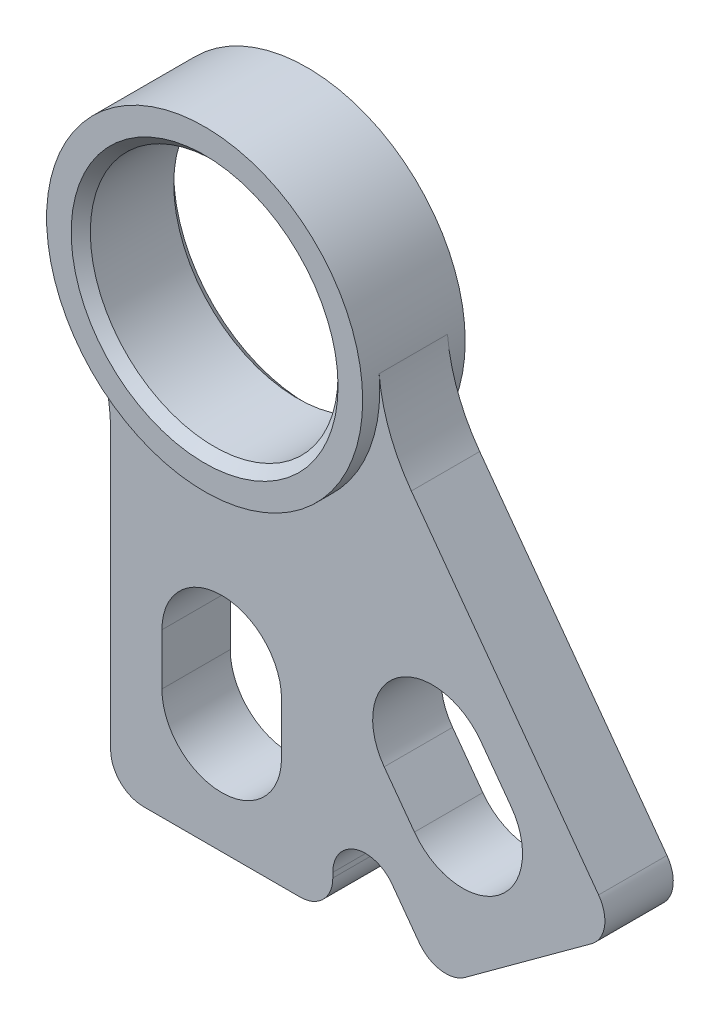
SolidWorks part; units mm, degrees
material "AISI 4130 Steel, annealed at 865C"
ref_plane "X-Y Datum" through (0, 0, 0) normal (0, 0, 1) x (1, 0, 0)
ref_plane "X-Z Datum" through (0, 0, 0) normal (0, 1, 0) x (1, 0, 0)
ref_plane "Y-Z Datum" through (0, 0, 0) normal (1, 0, 0) x (0, 0, -1)
sketch "Sketch1" plane through (0, 0, 0) normal (0, 0, 1) x (1, 0, 0)
  line L0 (0, -34.1313) -> (0, -29.3687) construction
  line L1 (-5.5562, -34.1313) -> (-5.5562, -29.3687)
  line L2 (5.5562, -34.1313) -> (5.5562, -29.3687)
  line L3 (22.3879, -30.632) -> (19.5777, -26.787) construction
  line L4 (17.902, -33.9106) -> (15.0918, -30.0656)
  line L5 (26.8737, -27.3535) -> (24.0635, -23.5085)
  line L6 (-10.3187, -15.7343) -> (-10.3187, -44.45)
  line L7 (-10.3187, -44.45) -> (10.3187, -44.45)
  line L10 (20.1457, -45.0517) -> (36.8075, -32.8742)
  line L11 (36.8075, -32.8742) -> (17.6152, -6.6144)
  line L13 (10.3187, -44.45) -> (10.3187, -31.606)
  line L14 (0, -39.6875) -> (0, -44.45) construction
  line L15 (25.6664, -35.1179) -> (28.4766, -38.9629) construction
  line L16 (25.4686, -25.431) -> (29.3137, -22.6208) construction
  line L17 (-5.5562, -31.75) -> (-10.3187, -31.75) construction
  line L18 (-10.3187, -19.05) -> (10.3187, -19.05) construction
  line L19 (10.3187, -19.05) -> (10.3187, -44.45) construction
  line L20 (5.5562, -31.75) -> (10.3187, -31.75) construction
  line L21 (0, -23.8125) -> (0, -19.05) construction
  line L22 (20.1457, -45.0517) -> (5.158, -24.5449) construction
  line L23 (5.158, -24.5449) -> (21.8198, -12.3674) construction
  line L24 (16.4969, -31.9881) -> (12.6519, -34.7983) construction
  line L25 (16.2991, -22.3012) -> (13.4889, -18.4561) construction
  line L29 (20.1457, -45.0517) -> (10.3187, -31.606)
  line L31 (219.5217, -300.3591) -> (0, 0) construction
  line L32 (0, -364.1414) -> (0, 0) construction
  circle A0 centre (0, 0) radius 11.5062
  arc A1 (-5.5562, -34.1313) -> (5.5562, -34.1313) centre (0, -34.1313) ccw
  arc A2 (5.5562, -29.3687) -> (-5.5562, -29.3687) centre (0, -29.3687) ccw
  arc A3 (17.902, -33.9106) -> (26.8737, -27.3535) centre (22.3879, -30.632) ccw
  arc A4 (24.0635, -23.5085) -> (15.0918, -30.0656) centre (19.5777, -26.787) ccw
  arc A5 (14.6215, 1.3227) -> (-12.5852, -7.5598) centre (0, 0) ccw
  arc A6 (17.6152, -6.6144) -> (14.6215, 1.3227) centre (30.4319, 2.7529) cw
  arc A7 (-10.3187, -15.7343) -> (-12.5852, -7.5598) centre (-26.1937, -15.7343) ccw
  arc A14 (-12.5852, -7.5598) -> (14.6215, 1.3227) centre (0, 0) ccw
  point P5 (0, -31.75)
  point P11 (20.9828, -28.7095)
  point P24 (28.4766, -38.9629)
  point P31 (0, -44.45)
  point P39 (25.6664, -35.1179)
  dimension "D1" = 23.0124
  dimension "D2" = 3.175
  dimension "D8" = 15.875
  dimension "D6" = 19.05
  dimension "D3" = 20.6375
  dimension "D4" = 4.7625
  dimension "D5" = 25.4
  dimension "D7" = 22.86
extrude "Boss-Extrude2" add sketch "Sketch1" along normal mid plane 9.525 contours A5 A14 A0 region at (-4.4276, 13.5615, 0)
extrude "Boss-Extrude3" add sketch "Sketch1<4>" along normal mid plane 6.35 contours A14 A7 L6 L7 L10 L11 A6 A4 L5 A3 L4 A2 L2 A1 L1 region at (9.6948, -26.454, 0)
sketch "Sketch1<4>" plane through (0, 0, 0) normal (0, 0, 1) x (1, 0, 0) same geometry as "Sketch1"
fillet "Fillet1" radius 3.048 5 edges at (-10.3187, -44.45, 0) (36.8075, -32.8742, 0) (10.3187, -31.606, 0) (10.3187, -44.45, 0) (20.1457, -45.0517, 0)
chamfer "Chamfer1" distance 0.889 angle 45 2 edges at (11.5062, 0, -4.7625) (11.5062, 0, 4.7625)
